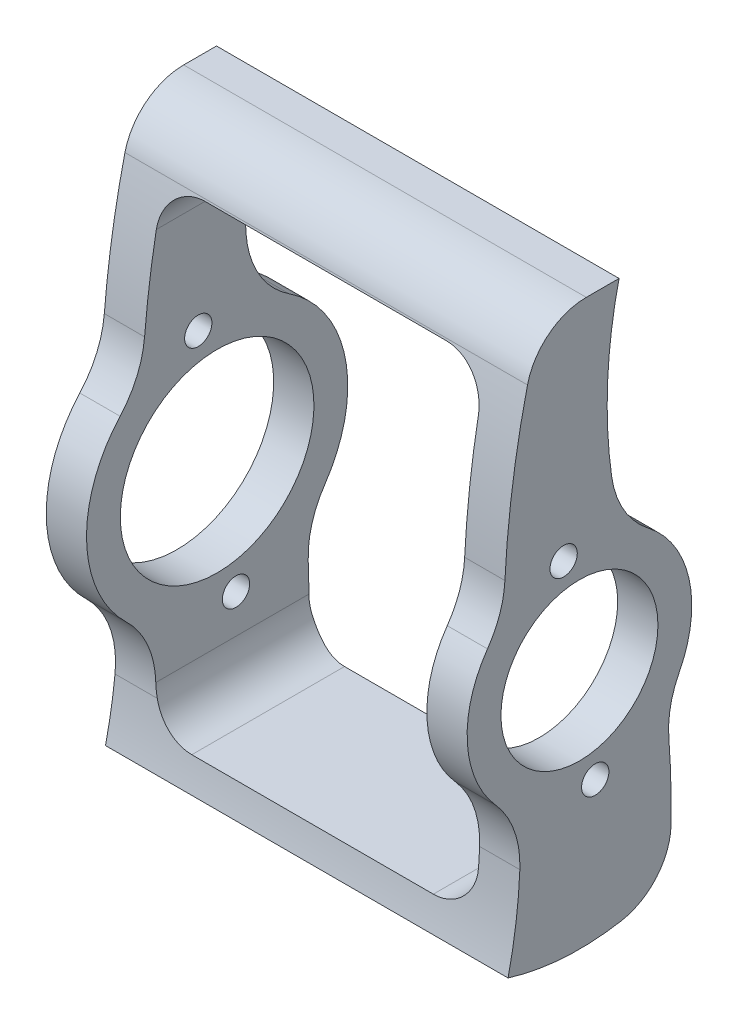
SolidWorks part; units mm, degrees
other "Markup2"
sketch "Sketch9" plane through (31.75, 50.4016, 20.35) normal (0.8402, 0.4575, 0.2911) x (0.3274, 0, -0.9449)
material "AISI 4340 Steel, normalized"
ref_plane "Front Plane" through (0, 0, 0) normal (0, 0, 1) x (1, 0, 0)
ref_plane "Top Plane" through (0, 0, 0) normal (0, 1, 0) x (1, 0, 0)
ref_plane "Right Plane" through (0, 0, 0) normal (1, 0, 0) x (0, 0, -1)
other "Center of Mass"
ref_plane "Plane1" through (-2.0281, 0, 0) normal (1, 0, 0) x (0, 0, -1)
sketch "Weapon Layout" plane through (-2.0281, 0, 0) normal (1, 0, 0) x (0, 0, -1)
  line L0 (-6.2484, 50.4143) -> (6.2484, 50.4143) construction
  line L1 (-11.2609, -36.3978) -> (14.119, -35.3873) construction
  line L2 (6.2484, 50.4143) -> (-5.4512, 0) construction
  line L3 (6.2484, 50.4143) -> (0, 0) construction
  line L4 (0, 0) -> (0, -35.9495) construction
  circle A0 centre (0, 0) radius 14 construction
  circle A1 centre (0, 0) radius 50.8 construction
  circle A2 centre (0, 0) radius 17.175 construction
  circle A3 centre (0, 0) radius 20.35 construction
  arc A4 (-6.2484, 50.4143) -> (-20.35, 0) centre (76.8181, 0) ccw construction
  arc A5 (25.0504, -28.707) -> (-25.4024, -28.3959) centre (0, 0) cw construction
  arc A6 (6.2484, 50.4143) -> (15.4079, 13.2936) centre (47.3713, 40.8709) ccw construction
  dimension "D1" = 28
  dimension "D2" = 101.6
  dimension "D3" = 3.175
  dimension "D4" = 6.35
  dimension "D5" = 12.4968
  dimension "D7" = 6
  dimension "D6" = 12.7
  dimension "D8" = 25.4
  dimension "D9" = 87.72
sketch "Sketch2" plane through (-2.0281, 0, 0) normal (1, 0, 0) x (0, 0, -1)
  line L0 (-6.2484, 50.4143) -> (6.2484, 50.4143)
  line L1 (-11.3224, -1.5644) -> (0, 0) construction
  line L2 (6.2484, 50.4143) -> (-5.4512, 0) construction
  line L3 (-11.5831, 0.9204) -> (-15.1384, 50.4143) construction
  arc A0 (-11.2609, -36.3978) -> (14.119, -35.3873) centre (0, 0) ccw
  arc A1 (-25.4024, -28.3959) -> (25.0504, -28.707) centre (0, 0) ccw construction
  arc A2 (-10.8995, -4.0268) -> (-11.5831, 0.9204) centre (26.419, 3.6503) cw
  arc A3 (9.7624, 6.6179) -> (11.7942, -0.0229) centre (-25.5032, -7.8024) cw
  arc A4 (-11.5831, 0.9204) -> (-6.2484, 50.4143) centre (127.7924, 10.9323) cw
  arc A5 (-10.8995, -4.0268) -> (-11.2609, -36.3978) centre (-85.5365, -19.3811) cw
  arc A6 (6.2484, 50.4143) -> (9.7624, 6.6179) centre (76.8178, 34.0373) ccw
  arc A7 (11.7942, -0.0229) -> (14.119, -35.3873) centre (-112.5302, -25.9546) cw
  circle A9 centre (0, 0) radius 11.43 construction
  point P25 (10.9299, 3.3439)
  dimension "D1" = 127
  dimension "D2" = 38.1
  dimension "D3" = 76.2
  dimension "D4" = 38.1
  dimension "D5" = 22.86
  dimension "D6" = 8.89
extrude "Boss-Extrude2" add sketch "Sketch2" along normal mid plane 63.5
sketch "Sketch3" plane through (0, 0, 0) normal (0, 0, 1) x (1, 0, 0)
  line L0 (29.7219, 50.4143) -> (-33.7781, 50.4143) construction
  line L1 (-27.4281, 42.7943) -> (23.3719, 42.7943)
  line L2 (-27.4281, 42.7943) -> (-27.4281, -31.75)
  line L3 (-27.4281, -31.75) -> (23.3719, -31.75)
  line L4 (23.3719, 42.7943) -> (23.3719, -31.75)
  line L6 (-33.7781, -38.1) -> (29.7219, -38.1) construction
  line L7 (-33.7781, 50.4143) -> (-33.7781, 0.9204) construction
  dimension "D4" = 6.35
  dimension "D1" = 7.62
  dimension "D3" = 6.35
  dimension "D2" = 6.35
extrude "Cut-Extrude1" cut sketch "Sketch3" against normal through all both and the other way through all
fillet "Fillet1" radius 6.35 4 edges at (-27.4281, 42.7943, 1.6785) (23.3719, 42.7943, 1.6785) (23.3719, -31.75, -1.9952) (-27.4281, -31.75, -1.9952)
fillet "Fillet3" radius 9.525 2 edges at (-2.0281, -35.3873, -14.119) (-2.0281, 50.4143, 6.2484)
sketch "Sketch6" plane through (-33.7781, 0, 0) normal (-1, 0, 0) x (0, 0, 1)
  circle A0 centre (0, 0) radius 20.604
  dimension "D1" = 41.208
extrude "Boss-Extrude3" add sketch "Sketch6" against normal up to surface (6.35 mm away) up to face at (-27.4281, 3.1884, 0.3076)
sketch "Sketch7" plane through (-33.7781, 0, 0) normal (-1, 0, 0) x (0, 0, 1)
  circle A0 centre (0, 0) radius 15.27
  arc A1 (9.3433, -18.3637) -> (11.8156, 16.8795) centre (0, 0) ccw construction
  dimension "D1" = 30.54
extrude "Cut-Extrude3" cut sketch "Sketch7" against normal up to next
sketch "Sketch10" plane through (29.7219, 0, 0) normal (1, 0, 0) x (0, 0, -1)
  circle A0 centre (0, 0) radius 17.7165
  dimension "D1" = 35.433
extrude "Boss-Extrude4" add sketch "Sketch10" against normal up to surface (6.35 mm away) up to face at (23.3719, 3.1884, 0.3076)
sketch "Sketch5" plane through (29.7219, 0, 0) normal (1, 0, 0) x (0, 0, -1)
  circle A0 centre (0, 0) radius 12.3825
  circle A1 centre (0, 0) radius 6.35 construction
  dimension "D1" = 12.7
  dimension "D2" = 24.765
extrude "Cut-Extrude2" cut sketch "Sketch5" against normal up to next
fillet "Fillet2" radius 15.24 8 edges at (-30.6031, 16.8795, 11.8156) (-30.6031, -18.3637, 9.3433) (-30.6031, -15.1114, -14.006) (-30.6031, 19.7734, -5.7912) (26.5469, 16.4667, -6.5361) (26.5469, -11.3248, -13.6243) (26.5469, -14.9769, 9.4639) (26.5469, 13.1019, 11.9254)
sketch "Sketch11" plane through (29.7219, 0, 0) normal (1, 0, 0) x (0, 0, -1)
  circle A0 centre (-2.4917, 16.1603) radius 1.8986
  circle A1 centre (2.4917, -16.1603) radius 1.8986 construction
  circle A2 centre (2.4917, -16.1603) radius 1.8987
  circle A4 centre (-2.4917, 16.1603) radius 1.8986 construction
hole_wizard "#6 Clearance Hole1" positions "Sketch12" profile "Sketch13" hole size "#6" standard "ANSI Inch"
sketch "Sketch12" plane through (-33.7781, 0, 0) normal (1, 0, 0) x (0, 0, -1)
  point P0 (-2.9763, 19.3027)
  point P3 (2.9763, -19.3027)
sketch "Sketch13" plane through (-33.7781, 19.3027, 2.9763) normal (0, 1, 0) x (0, 0, 1)
  line L0 (0, 0) -> (0, 8.9134)
  line L1 (0, 8.9134) -> (2.1526, 7.62)
  line L2 (2.1526, 7.62) -> (2.1526, 0)
  line L5 (2.1526, 0) -> (0, 0)
  line L10 (0, 8.9134) -> (-2.1527, 7.62) construction
  line L11 (0, -6.35) -> (0, 107.95) construction
  dimension "Hole Dia." = 4.3053
  dimension "Hole Depth" = 7.62
  dimension "Drill Angle" = 118
hole_wizard "#6 Clearance Hole2" positions "Sketch14" profile "Sketch16" hole size "#6" standard "ANSI Inch" end condition up to next
sketch "Sketch14" plane through (29.7219, 0, 0) normal (1, 0, 0) x (0, 0, -1)
  point P0 (-2.4917, 16.1603)
  point P3 (2.4917, -16.1603)
sketch "Sketch16" plane through (29.7219, 16.1603, 2.4917) normal (0, 1, 0) x (0, 0, -1)
  line L0 (0, 0) -> (0, 6.35)
  line L1 (0, 6.35) -> (2.1526, 6.35)
  line L2 (2.1526, 6.35) -> (2.1526, 0)
  line L5 (2.1526, 0) -> (0, 0)
  line L11 (0, -6.35) -> (0, 107.95) construction
  dimension "Thru Hole Dia." = 4.3053
  dimension "Thru Hole Depth" = 6.35
other "Center of Mass Reference Point1"
equation "\"D1@Weapon Layout\" = 28mm"
equation "\"D1@Sketch6\"=\"bearing OD L\"+.42in+0.1in"
equation "\"D2@Sketch3\"=\"D3@Sketch3\""
equation "\"D1@Sketch7\"=\"bearing OD L\"+0.1in"
equation "\"D2@Sketch5\"=\"bearing OD R\" + .1"
equation "\"D1@Sketch10\"=\"bearing OD R\" + 0.42 + .1"
equation "\"bearing OD R\"= 7 / 8"
equation "\"bearing OD L\"= 28mm"
